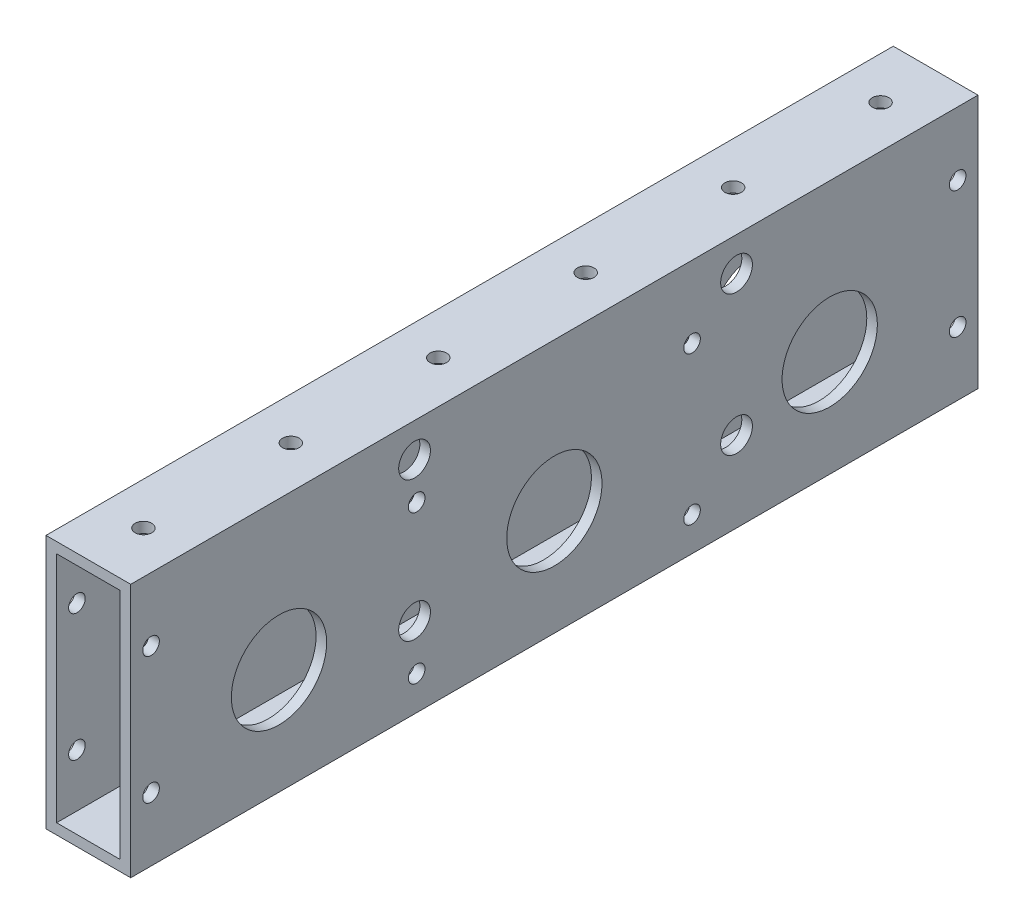
SolidWorks part; units mm, degrees
material "6061-T6 (SS)"
ref_plane "Front Plane" through (0, 0, 0) normal (0, 0, 1) x (1, 0, 0)
ref_plane "Top Plane" through (0, 0, 0) normal (0, 1, 0) x (1, 0, 0)
ref_plane "Right Plane" through (0, 0, 0) normal (1, 0, 0) x (0, 0, -1)
sketch "Sketch1" plane through (0, 0, 0) normal (1, 0, 0) x (0, 0, -1)
  line L1 (-127, 38.1) -> (127, 38.1)
  line L2 (-127, 38.1) -> (-127, -38.1)
  line L3 (-127, -38.1) -> (127, -38.1)
  line L4 (127, 38.1) -> (127, -38.1)
  line L5 (-127, 38.1) -> (127, -38.1) construction
  line L6 (-127, -38.1) -> (127, 38.1) construction
  point P0 (0, 0)
  dimension "D1" = 76.2
  dimension "D2" = 254
extrude "Boss-Extrude1" add sketch "Sketch1" along normal blind 25.4
shell "Shell1" thickness 3.175 removed face at (12.7, 0, -127) removed face at (12.7, 0, 127)
sketch "Sketch2" plane through (25.4, 0, 0) normal (1, 0, 0) x (0, 0, -1)
  line L0 (-127, -38.1) -> (127, -38.1) construction
  line L1 (-82.55, -6.35) -> (0, -6.35) construction
  line L2 (-41.275, -27.94) -> (-41.275, -6.35) construction
  line L3 (0, -6.35) -> (82.55, -6.35) construction
  line L4 (41.275, -27.94) -> (41.275, -6.35) construction
  line L5 (127, 38.1) -> (-127, 38.1) construction
  line L6 (54.61, 27.94) -> (-41.91, 27.94) construction
  line L7 (54.61, 27.94) -> (54.61, -13.97) construction
  line L8 (54.61, -13.97) -> (-41.91, -13.97) construction
  line L9 (-41.91, 27.94) -> (-41.91, -13.97) construction
  line L10 (-127, -38.1) -> (127, -38.1) construction
  circle A0 centre (0, -6.35) radius 14.2875
  circle A1 centre (-82.55, -6.35) radius 14.2875
  circle A2 centre (82.55, -6.35) radius 14.2875
  circle A3 centre (-82.55, -6.35) radius 38.1 construction
  circle A4 centre (0, -6.35) radius 38.1 construction
  circle A5 centre (82.55, -6.35) radius 38.1 construction
  circle A6 centre (-41.275, -27.94) radius 6.35 construction
  circle A7 centre (41.275, -27.94) radius 6.35 construction
  circle A8 centre (-41.275, 16.51) radius 6.35 construction
  circle A9 centre (41.275, 16.51) radius 6.35 construction
  point P11 (0, 0)
  dimension "D1" = 28.575
  dimension "D5" = 76.2
  dimension "D7" = 12.7
  dimension "D2" = 31.75
  dimension "D3" = 82.55
  dimension "D4" = 82.55
  dimension "D6" = 0
  dimension "D8" = 10.16
  dimension "D9" = 44.45
  dimension "D10" = 41.91
  dimension "D11" = 96.52
  dimension "D12" = 10.16
  dimension "D13" = 24.13
extrude "Cut-Extrude1" cut sketch "Sketch2" against normal through all
sketch "Sketch3" plane through (25.4, 0, 0) normal (1, 0, 0) x (0, 0, -1)
  line L0 (-120.904, 19.05) -> (-120.904, -19.05) construction
  line L1 (-127, 38.1) -> (-127, -38.1) construction
  point P2 (-120.904, 0)
  point P3 (-127, 0)
  dimension "D1" = 38.1
  dimension "D2" = 6.096
hole_wizard "#10 Clearance Hole1" positions "Sketch4" profile "Sketch6" hole size "#10" standard "ANSI Inch" end condition through all
sketch "Sketch4" plane through (25.4, 0, 0) normal (1, 0, 0) x (0, 0, -1)
  point P0 (-120.904, 19.05)
  point P3 (-120.904, -19.05)
sketch "Sketch6" plane through (25.4, 19.05, 120.904) normal (0, 1, 0) x (0, 0, -1)
  line L0 (0, 0) -> (0, 25.4)
  line L1 (0, 25.4) -> (2.4892, 25.4)
  line L2 (2.4892, 25.4) -> (2.4892, 0)
  line L5 (2.4892, 0) -> (0, 0)
  line L11 (0, -6.35) -> (0, 107.95) construction
  dimension "Thru Hole Dia." = 4.9784
  dimension "Thru Hole Depth" = 25.4
mirror "Mirror1" about plane through (0, 0, 0) normal (0, 0, 1) of "#10 Clearance Hole1"
hole_wizard "#10 Clearance Hole2" positions "Sketch7" profile "Sketch8" hole size "#10" standard "ANSI Inch" end condition through all
sketch "Sketch7" plane through (25.4, 0, 0) normal (1, 0, 0) x (0, 0, -1)
  point P0 (-41.275, -27.94)
  point P3 (41.275, -27.94)
  point P7 (-41.275, 16.51)
  point P10 (41.275, 16.51)
sketch "Sketch8" plane through (25.4, -27.94, 41.275) normal (0, 1, 0) x (0, 0, -1)
  line L0 (0, 0) -> (0, 25.4)
  line L1 (0, 25.4) -> (2.4892, 25.4)
  line L2 (2.4892, 25.4) -> (2.4892, 0)
  line L5 (2.4892, 0) -> (0, 0)
  line L11 (0, -6.35) -> (0, 107.95) construction
  dimension "Thru Hole Dia." = 4.9784
  dimension "Thru Hole Depth" = 25.4
hole_wizard "3/8 (0.375) Diameter Hole1" positions "Sketch9" profile "Sketch10" hole size "3/8" standard "ANSI Inch"
sketch "Sketch9" plane through (0, 0, 0) normal (-1, 0, 0) x (0, 0, 1)
  point P0 (-41.275, -27.94)
  point P3 (41.275, -27.94)
  point P7 (41.275, 16.51)
  point P10 (-41.275, 16.51)
sketch "Sketch10" plane through (0, -27.94, -41.275) normal (0, 1, 0) x (0, 0, 1)
  line L0 (0, 0) -> (0, 15.5616)
  line L1 (0, 15.5616) -> (4.7625, 12.7)
  line L2 (4.7625, 12.7) -> (4.7625, 0)
  line L5 (4.7625, 0) -> (0, 0)
  line L10 (0, 15.5616) -> (-4.7625, 12.7) construction
  line L11 (0, -6.35) -> (0, 107.95) construction
  dimension "Hole Dia." = 9.525
  dimension "Hole Depth" = 12.7
  dimension "Drill Angle" = 118
hole_wizard "3/8 (0.375) Diameter Hole2" positions "Sketch11" profile "Sketch12" hole size "3/8" standard "ANSI Inch"
sketch "Sketch11" plane through (25.4, 0, 0) normal (1, 0, 0) x (0, 0, -1)
  point P0 (-41.91, 27.94)
  point P3 (54.61, 27.94)
  point P6 (54.61, -13.97)
  point P9 (-41.91, -13.97)
sketch "Sketch12" plane through (25.4, 27.94, 41.91) normal (0, 1, 0) x (0, 0, -1)
  line L0 (0, 0) -> (0, 15.5616)
  line L1 (0, 15.5616) -> (4.7625, 12.7)
  line L2 (4.7625, 12.7) -> (4.7625, 0)
  line L5 (4.7625, 0) -> (0, 0)
  line L10 (0, 15.5616) -> (-4.7625, 12.7) construction
  line L11 (0, -6.35) -> (0, 107.95) construction
  dimension "Hole Dia." = 9.525
  dimension "Hole Depth" = 12.7
  dimension "Drill Angle" = 118
hole_wizard "#10 Clearance Hole3" positions "Sketch13" profile "Sketch14" hole size "#10" standard "ANSI Inch"
sketch "Sketch13" plane through (0, 0, 0) normal (-1, 0, 0) x (0, 0, 1)
  point P0 (41.91, 27.94)
  point P3 (-54.61, 27.94)
  point P6 (-54.61, -13.97)
  point P9 (41.91, -13.97)
sketch "Sketch14" plane through (0, 27.94, 41.91) normal (0, 1, 0) x (0, 0, 1)
  line L0 (0, 0) -> (0, 14.1957)
  line L1 (0, 14.1957) -> (2.4892, 12.7)
  line L2 (2.4892, 12.7) -> (2.4892, 0)
  line L5 (2.4892, 0) -> (0, 0)
  line L10 (0, 14.1957) -> (-2.4892, 12.7) construction
  line L11 (0, -6.35) -> (0, 107.95) construction
  dimension "Hole Dia." = 4.9784
  dimension "Hole Depth" = 12.7
  dimension "Drill Angle" = 118
sketch "Sketch15" plane through (0, -38.1, 0) normal (0, -1, 0) x (1, 0, 0)
  line L0 (12.7, 110.49) -> (12.7, -110.49) construction
  line L1 (25.4, 127) -> (25.4, -127) construction
  line L2 (25.4, 127) -> (0, 127) construction
  point P2 (25.4, 0)
  point P3 (12.7, 0)
  point P7 (12.7, 127)
  dimension "D1" = 16.51
hole_wizard "#10 Clearance Hole4" positions "Sketch16" profile "Sketch17" hole size "#10" standard "ANSI Inch" end condition through all
sketch "Sketch16" plane through (0, -38.1, 0) normal (0, -1, 0) x (-1, 0, 0)
  point P0 (-12.7, -110.49)
  point P3 (-12.7, 110.49)
sketch "Sketch17" plane through (12.7, -38.1, 110.49) normal (1, 0, 0) x (0, 0, -1)
  line L0 (0, 0) -> (0, 76.2)
  line L1 (0, 76.2) -> (2.4892, 76.2)
  line L2 (2.4892, 76.2) -> (2.4892, 0)
  line L5 (2.4892, 0) -> (0, 0)
  line L11 (0, -6.35) -> (0, 107.95) construction
  dimension "Thru Hole Dia." = 4.9784
  dimension "Thru Hole Depth" = 76.2
sketch "Sketch18" plane through (0, 38.1, 0) normal (0, 1, 0) x (1, 0, 0)
  line L0 (25.4, 127) -> (0, 127) construction
  line L1 (25.4, 127) -> (25.4, -127) construction
  point P0 (12.7, 127)
  point P1 (12.7, 66.294)
  point P4 (25.4, 0)
  point P6 (12.7, 22.098)
  dimension "D1" = 44.196
  dimension "D2" = 22.098
hole_wizard "#10 Clearance Hole5" positions "Sketch19" profile "Sketch21" hole size "#10" standard "ANSI Inch" end condition through all
sketch "Sketch19" plane through (0, 38.1, 0) normal (0, 1, 0) x (1, 0, 0)
  point P0 (12.7, 66.294)
  point P4 (12.7, 22.098)
sketch "Sketch21" plane through (12.7, 38.1, -66.294) normal (1, 0, 0) x (0, 0, 1)
  line L0 (0, 0) -> (0, 76.2)
  line L1 (0, 76.2) -> (2.4892, 76.2)
  line L2 (2.4892, 76.2) -> (2.4892, 0)
  line L5 (2.4892, 0) -> (0, 0)
  line L11 (0, -6.35) -> (0, 107.95) construction
  dimension "Thru Hole Dia." = 4.9784
  dimension "Thru Hole Depth" = 76.2
mirror "Mirror2" about plane through (0, 0, 0) normal (0, 0, 1) of "#10 Clearance Hole5"
